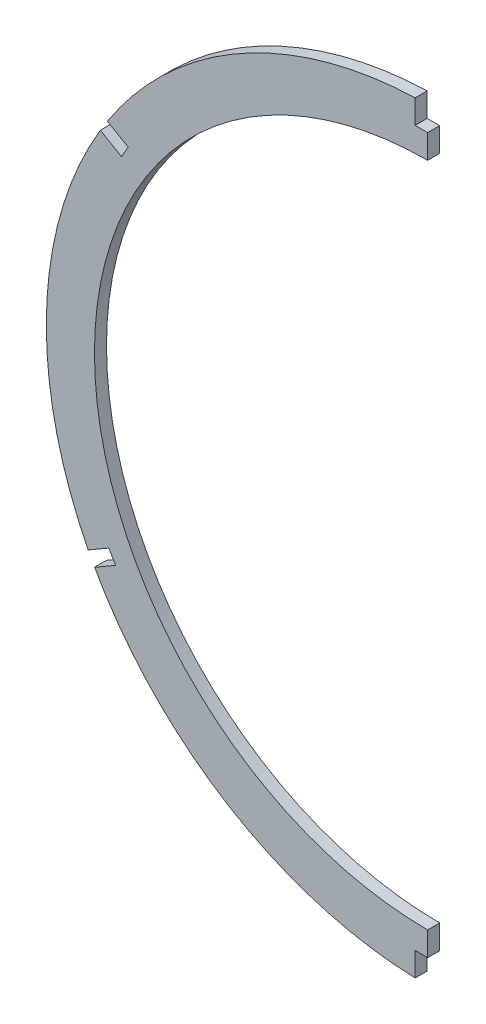
SolidWorks part; units mm, degrees
material "Balsa"
ref_plane "Front Plane" through (0, 0, 0) normal (0, 0, 1) x (1, 0, 0)
ref_plane "Top Plane" through (0, 0, 0) normal (0, 1, 0) x (1, 0, 0)
ref_plane "Right Plane" through (0, 0, 0) normal (1, 0, 0) x (0, 0, -1)
sketch "Sketch2" plane through (0, 0, 0) normal (0, 0, 1) x (1, 0, 0)
  line L0 (0, 0) -> (0, 240.9936) construction
  line L1 (-1.7839, 106.6642) -> (-1.7839, 99.822) construction
  line L2 (1.7839, 106.6642) -> (1.7839, 99.822) construction
  line L3 (-1.7839, 99.822) -> (1.7839, 99.822) construction
  line L4 (-87.7705, -42.8471) -> (-87.8712, -42.9053) construction
  line L5 (-604.1774, -338.907) -> (0, 9.8743) construction
  line L6 (-89.5483, -39.7674) -> (-83.8289, -36.4657) construction
  line L7 (-87.7705, -42.8471) -> (-82.0511, -39.5454) construction
  line L8 (-83.8289, -36.4657) -> (-82.0511, -39.5454) construction
  line L9 (604.1774, -338.907) -> (0, 9.8743) construction
  line L10 (87.7705, -42.8471) -> (82.0511, -39.5454) construction
  line L11 (87.7705, -42.8471) -> (87.8712, -42.9053) construction
  line L12 (89.5483, -39.7674) -> (83.8289, -36.4657) construction
  line L13 (83.8289, -36.4657) -> (82.0511, -39.5454) construction
  arc A0 (-7.652, 93.6463) -> (7.652, 93.6463) centre (0, 6.0782) ccw
  arc A1 (-1.7839, 106.6642) -> (-89.5483, -39.7674) centre (0, 6.0782) ccw
  arc A6 (-1.778, 93.962) -> (-7.652, 93.6463) centre (0, 6.0782) ccw
  circle A7 centre (0, 6.0782) radius 87.9018 construction
  arc A8 (0, 93.98) -> (-1.778, 93.962) centre (0, 6.0782) ccw
  arc A9 (1.778, 93.962) -> (0, 93.98) centre (0, 6.0782) ccw
  arc A10 (1.778, 93.962) -> (0, 93.98) centre (0, 6.0782) ccw construction
  arc A12 (7.652, 93.6463) -> (1.778, 93.962) centre (0, 6.0782) ccw
  arc A13 (0, 93.98) -> (-1.778, 93.962) centre (0, 6.0782) ccw construction
  arc A15 (7.652, 93.6463) -> (1.778, 93.962) centre (0, 6.0782) ccw construction
  arc A16 (-1.778, 93.962) -> (-7.652, 93.6463) centre (0, 6.0782) ccw construction
  arc A17 (0, 106.68) -> (-1.7839, 106.6642) centre (0, 6.0782) ccw
  circle A18 centre (0, 6.0782) radius 100.6018 construction
  arc A19 (1.7839, 106.6642) -> (0, 106.68) centre (0, 6.0782) ccw
  arc A20 (-87.8712, -42.9053) -> (87.8712, -42.9053) centre (0, 6.0782) ccw
  arc A21 (-89.5483, -39.7674) -> (-88.7234, -41.3442) centre (0, 6.0782) ccw
  arc A22 (-88.7234, -41.3442) -> (-87.8712, -42.9053) centre (0, 6.0782) ccw
  arc A23 (87.8712, -42.9053) -> (88.7234, -41.3442) centre (0, 6.0782) ccw
  arc A24 (89.5483, -39.7674) -> (1.7839, 106.6642) centre (0, 6.0782) ccw
  arc A25 (88.7234, -41.3442) -> (89.5483, -39.7674) centre (0, 6.0782) ccw
  point P25 (0, 99.822)
  dimension "D3" = 119.997
  dimension "D8" = 12.7
  dimension "D6" = 87.9018
  dimension "D2" = 1.7839
  dimension "D4" = 9.8743
  dimension "D5" = 3.556
  dimension "D1" = 93.98
  dimension "D7" = 5.842
  dimension "D9" = 6.604
  dimension "D10" = 3.556
extrude "Boss-Extrude1" add sketch "Sketch2" against normal blind 3.175
sketch "Sketch3" plane through (0, 0, 0) normal (1, 0, 0) x (0, 0, -1)
  line L5 (-72.4915, 152.7087) -> (76.812, 152.7087)
  line L6 (-72.4915, 152.7087) -> (-72.4915, -135.9702)
  line L7 (-72.4915, -135.9702) -> (76.812, -135.9702)
  line L8 (76.812, 152.7087) -> (76.812, -135.9702)
extrude "Cut-Extrude1" cut sketch "Sketch3" along normal through all
sketch "Sketch4" plane through (0, 0, 0) normal (0, 0, 1) x (1, 0, 0)
  line L0 (-88.1091, 62.7761) -> (-78.9966, 57.515)
  line L3 (-89.8744, 59.7185) -> (-88.1091, 62.7761)
  line L4 (0, 9.8679) -> (0, -96.8576) construction
  line L5 (0, 0) -> (0, 151.9186) construction
  line L6 (-88.9918, 61.2473) -> (-79.8792, 55.9862) construction
  line L7 (-89.8744, 59.7185) -> (-80.7619, 54.4574)
  line L8 (-80.7619, 54.4574) -> (-78.9966, 57.515)
  line L9 (-79.8792, 55.9862) -> (0, 9.8679) construction
  line L10 (0, 9.8679) -> (-60.4839, 9.8679) construction
  line L11 (-88.9918, -41.5115) -> (-79.8792, -36.2504) construction
  line L12 (-84.095, -36.646) -> (-82.3297, -39.7036)
  line L13 (-92.2228, -41.3386) -> (-84.095, -36.646)
  line L14 (-92.2228, -41.3386) -> (-90.4575, -44.3962)
  line L15 (-90.4575, -44.3962) -> (-82.3297, -39.7036)
  line L16 (-79.8792, -36.2504) -> (0, 9.8679) construction
  line L17 (0, -88.1737) -> (-3.302, -88.1737)
  line L18 (-3.302, -88.1737) -> (-3.302, -95.6228)
  line L20 (-3.302, -95.6228) -> (0, -95.6228)
  line L21 (0, -95.6228) -> (0, -88.1737)
  line L22 (-3.302, 110.2958) -> (0, 110.2958)
  line L23 (-3.302, 110.2958) -> (-3.302, 100.33)
  line L24 (-3.302, 100.33) -> (0, 100.33)
  line L25 (0, 110.2958) -> (0, 100.33)
  point P2 (-74.38, 52.8112)
  point P12 (-83.2124, -38.1748)
  point P19 (-77.7131, -34.9998)
  point P24 (0, -81.8237)
  point P25 (0, 0)
  point P27 (0, 93.98)
  dimension "D1" = 60
  dimension "D2" = 9.8679
  dimension "D3" = 3.5306
  dimension "D4" = 85.8866
  dimension "D5" = 6.35
  dimension "D6" = 89.7354
  dimension "D7" = 6.35
  dimension "D8" = 3.5306
  dimension "D9" = 3.302
  dimension "D10" = 91.6916
  dimension "D11" = 6.35
  dimension "D12" = 84.1121
  dimension "D13" = 6.35
  dimension "D14" = 3.302
extrude "Cut-Extrude2" cut sketch "Sketch4" against normal through all
